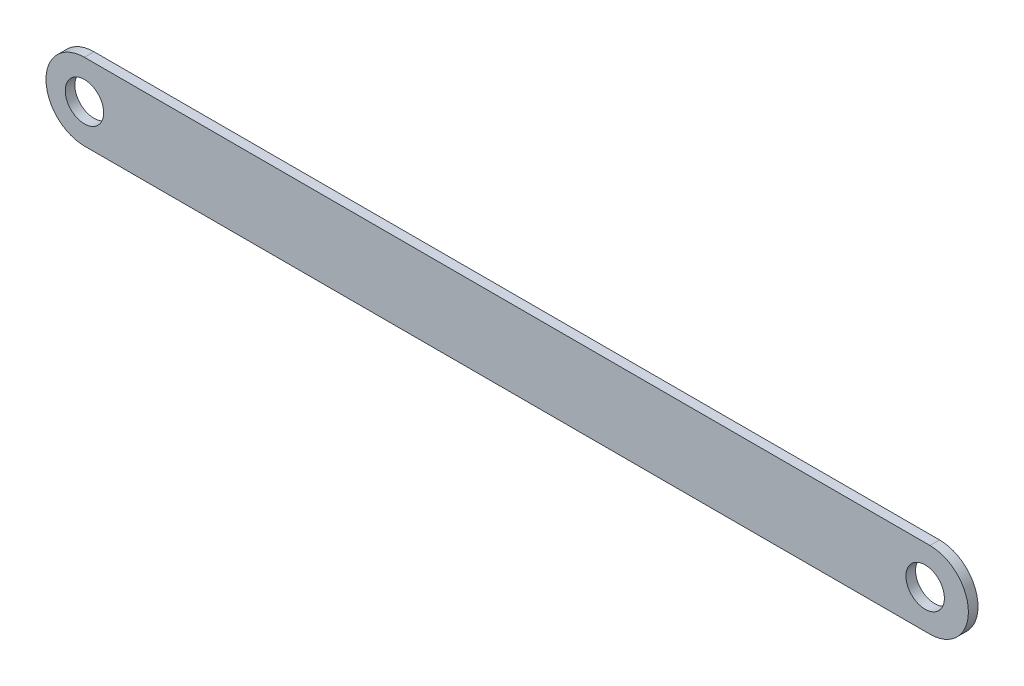
SolidWorks part; units mm, degrees
ref_plane "Front Plane" through (0, 0, 0) normal (0, 0, 1) x (1, 0, 0)
ref_plane "Top Plane" through (0, 0, 0) normal (0, 1, 0) x (1, 0, 0)
ref_plane "Right Plane" through (0, 0, 0) normal (1, 0, 0) x (0, 0, -1)
sketch "Sketch1" plane through (0, 0, 0) normal (0, 0, 1) x (1, 0, 0)
  line L0 (0, 25.4) -> (558.8, 25.4)
  line L1 (0, -25.4) -> (558.8, -25.4)
  arc A0 (0, 25.4) -> (0, -25.4) centre (0, 0) ccw
  arc A1 (558.8, -25.4) -> (558.8, 25.4) centre (558.8, 0) ccw
extrude "Boss-Extrude1" add sketch "Sketch1" along normal mid plane 6.35
sketch "Sketch2" plane through (0, 0, 3.175) normal (0, 0, 1) x (1, 0, 0)
  line L0 (0, 0) -> (555.625, 0)
  circle A0 centre (0, 0) radius 12.7
  circle A1 centre (555.625, 0) radius 12.7
extrude "Cut-Extrude1" cut sketch "Sketch2" against normal through all contours A0 | A1 region at (555.625, 12.3408, 3.175) region at (-12.3408, 0, 3.175)
